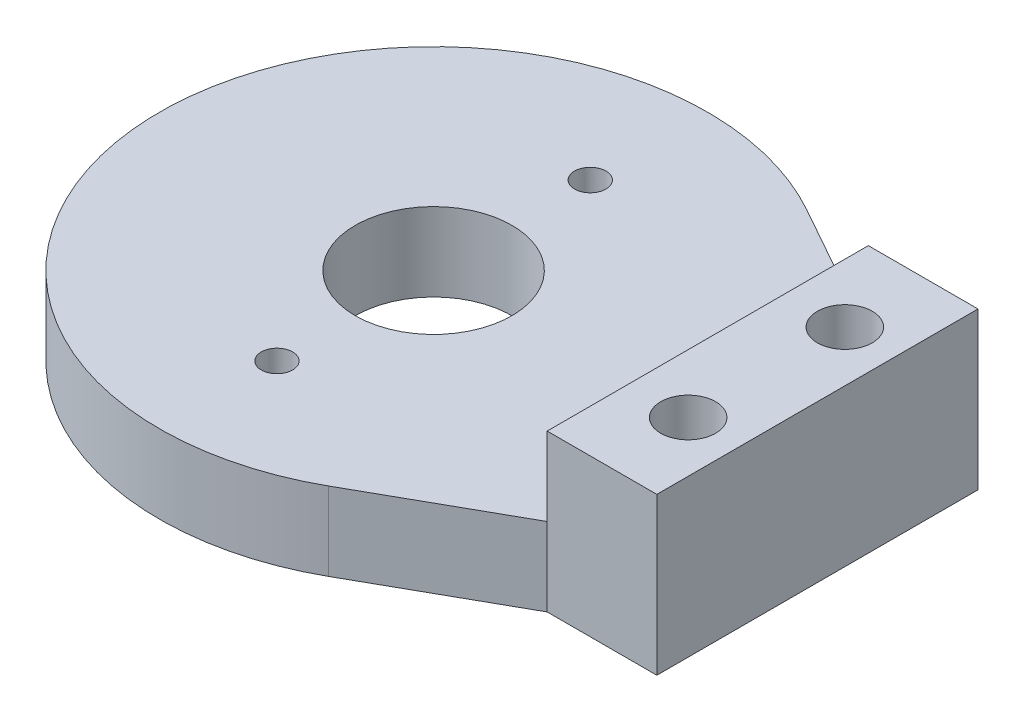
SolidWorks part; units mm, degrees
ref_plane "Front" through (0, 0, 0) normal (0, 0, 1) x (1, 0, 0)
ref_plane "Top" through (0, 0, 0) normal (0, 1, 0) x (1, 0, 0)
ref_plane "Right" through (0, 0, 0) normal (1, 0, 0) x (0, 0, -1)
sketch "Sketch1" plane through (0, 0, 0) normal (0, 1, 0) x (1, 0, 0)
  line L1 (0, 0) -> (7, 0)
  line L2 (0, 0) -> (0, -20.5)
  line L3 (0, -20.5) -> (7, -20.5)
  line L4 (7, 0) -> (7, -20.5)
  dimension "D1" = 7
  dimension "D2" = 20.5
extrude "mountingBase" add sketch "Sketch1" along normal blind 10
sketch "Sketch2" plane through (0, 10, 0) normal (0, 1, 0) x (1, 0, 0)
  line L0 (0, 0) -> (0, -20.5) construction
  line L1 (0, -10.25) -> (7, -10.25) construction
  line L2 (7, -20.5) -> (7, 0) construction
  line L3 (7, 0) -> (0, 0) construction
  circle A0 centre (3.75, -5.25) radius 1.75
  circle A1 centre (3.75, -15.25) radius 1.75
  dimension "D2" = 3.5
  dimension "D1" = 3.75
  dimension "D3" = 5.25
extrude "mountingHoles" cut sketch "Sketch2" against normal blind 10
sketch "Sketch3" plane through (0, 0, 0) normal (0, 1, 0) x (1, 0, 0)
  line L0 (0, 0) -> (0, -20.5) construction
  line L1 (0, 0) -> (-8.9401, 5.0136)
  line L2 (0, -20.5) -> (-8.9401, -25.5136)
  line L3 (0, 0) -> (0, -20.5)
  arc A0 (-8.9401, 5.0136) -> (-8.9401, -25.5136) centre (-17.5, -10.25) ccw
  point P4 (0, -10.25)
  dimension "D1" = 35
extrude "hornTab" add sketch "Sketch3" along normal blind 5
sketch "Sketch4" plane through (0, 5, 0) normal (0, 1, 0) x (1, 0, 0)
  line L0 (-17.5, -10.25) -> (-35, -10.25) construction
  circle A0 centre (-17.5, -10.25) radius 17.5 construction
  arc A1 (-8.9401, 5.0136) -> (-8.9401, -25.5136) centre (-17.5, -10.25) ccw construction
  circle A2 centre (-17.5, -0.25) radius 1
  circle A3 centre (-17.5, -20.25) radius 1
  circle A4 centre (-17.5, -10.25) radius 5
  dimension "D1" = 2
  dimension "D3" = 10
  dimension "D2" = 10
extrude "hornMountingHoles" cut sketch "Sketch4" against normal blind 5
